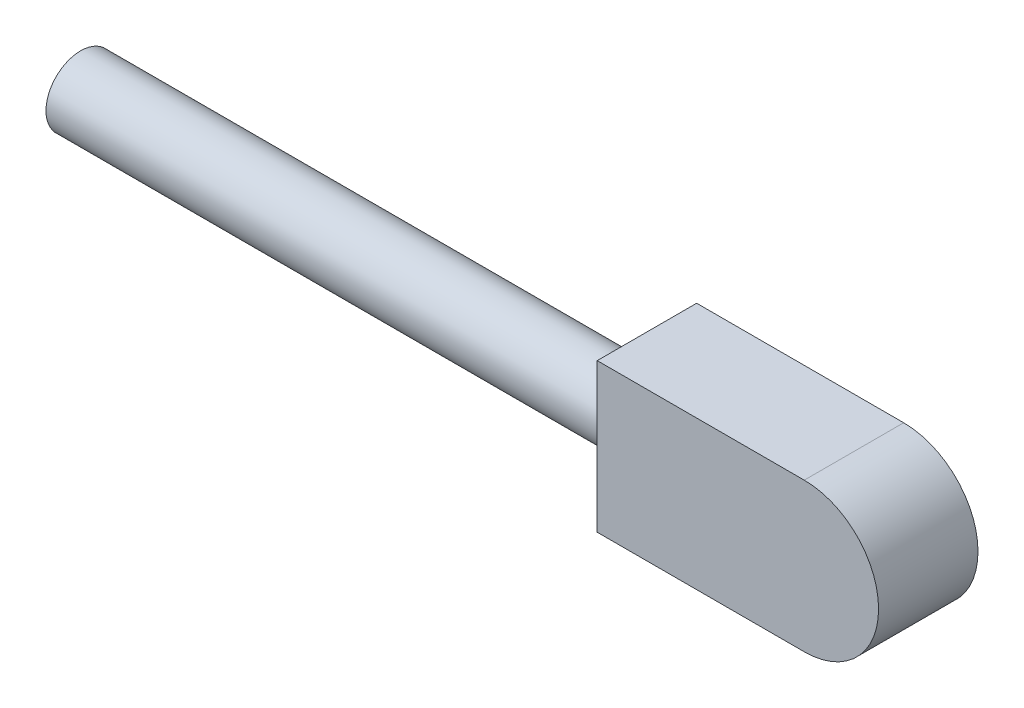
SolidWorks part; units mm, degrees
ref_plane "Front view" through (0, 0, 0) normal (0, 0, 1) x (1, 0, 0)
ref_plane "Top view" through (0, 0, 0) normal (0, 1, 0) x (1, 0, 0)
ref_plane "Side view" through (0, 0, 0) normal (1, 0, 0) x (0, 0, -1)
sketch "Sketch2" plane through (-3856.2967, 0, 6663.1981) normal (0, 1, 0) x (1, 0, 0)
  line L0 (3040.1244, 6663.1981) -> (3856.2967, 6663.1981)
  line L1 (4043.809, 6703.1981) -> (3856.2967, 6703.1981)
  line L2 (4043.809, 6623.1981) -> (3856.2967, 6623.1981)
  line L3 (3856.2967, 6703.1981) -> (3856.2967, 6623.1981)
  line L4 (3856.2967, 6635.6981) -> (3840.2967, 6635.6981)
  line L5 (3851.2967, 6635.6981) -> (3856.2966, 6630.6981)
  line L6 (3856.2967, 6635.6981) -> (3851.2967, 6635.6981)
  line L7 (3856.2966, 6630.6981) -> (3856.2967, 6635.6981)
  line L8 (3856.2967, 6690.6981) -> (3840.2967, 6690.6981)
  line L9 (3856.2966, 6695.6981) -> (3851.2967, 6690.6981)
  line L10 (3856.2967, 6690.6981) -> (3856.2966, 6695.6981)
  line L11 (3851.2967, 6690.6981) -> (3856.2967, 6690.6981)
sketch "Sketch3" plane through (-9482.0455, -5288.969, 0) normal (0, 0, 1) x (1, 0, 0)
  line L1947 (9537.2698, 5438.969) -> (9426.8132, 5502.7412)
  line L1958 (10135.0455, 5288.969) -> (9482.0455, 5288.969)
  line L2105 (9482.0455, 5288.969) -> (9482.0455, 5456.969)
  line L2178 (9651.7783, 5243.9695) -> (9653.5105, 5240.9693)
  line L2179 (9648.3136, 5243.969) -> (9651.7777, 5243.969)
  line L2180 (9646.5818, 5240.9694) -> (9648.3139, 5243.9696)
  line L2181 (9648.3137, 5237.969) -> (9646.5816, 5240.969)
  line L2182 (9651.7777, 5237.9688) -> (9648.3136, 5237.9688)
  line L2183 (9653.5101, 5240.9696) -> (9651.7779, 5237.9694)
  line L2184 (9688.1498, 5312.9695) -> (9689.882, 5315.9697)
  line L2185 (9689.8826, 5309.9691) -> (9688.1505, 5312.9692)
  line L2186 (9693.3463, 5309.9692) -> (9689.8819, 5309.9692)
  line L2187 (9695.0787, 5312.9693) -> (9693.3466, 5309.9693)
  line L2188 (9693.3469, 5315.9693) -> (9695.079, 5312.9693)
  line L2189 (9689.8819, 5315.9692) -> (9693.3462, 5315.9692)
  line L2190 (9689.8826, 5267.97) -> (9693.347, 5267.97)
  line L2191 (9688.1507, 5264.9691) -> (9689.8827, 5267.9692)
  line L2192 (9689.8826, 5261.9696) -> (9688.1504, 5264.9698)
  line L2193 (9693.3469, 5261.9693) -> (9689.8828, 5261.9693)
  line L2194 (9695.0791, 5264.969) -> (9693.347, 5261.969)
  line L2195 (9693.3465, 5267.9698) -> (9695.0787, 5264.9696)
  line L2196 (9648.3126, 5333.9686) -> (9646.5805, 5336.9688)
  line L2197 (9651.7774, 5333.969) -> (9648.3133, 5333.969)
  line L2198 (9653.5092, 5336.9687) -> (9651.777, 5333.9685)
  line L2199 (9651.7773, 5339.9691) -> (9653.5093, 5336.9691)
  line L2200 (9648.3133, 5339.9693) -> (9651.7774, 5339.9693)
  line L2201 (9646.5809, 5336.9685) -> (9648.313, 5339.9687)
  line L2202 (9610.2083, 5309.9681) -> (9606.744, 5309.9681)
  line L2203 (9611.9403, 5312.9689) -> (9610.2083, 5309.9689)
  line L2204 (9610.2084, 5315.9685) -> (9611.9406, 5312.9683)
  line L2205 (9606.7441, 5315.9688) -> (9610.2082, 5315.9688)
  line L2206 (9605.0119, 5312.9691) -> (9606.7439, 5315.9691)
  line L2207 (9606.7445, 5309.9683) -> (9605.0123, 5312.9685)
  line L2208 (9611.9412, 5264.9686) -> (9610.209, 5261.9684)
  line L2209 (9610.2084, 5267.9689) -> (9611.9404, 5264.9689)
  line L2210 (9606.7447, 5267.9689) -> (9610.2091, 5267.9689)
  line L2211 (9605.0123, 5264.9688) -> (9606.7443, 5267.9688)
  line L2212 (9606.7441, 5261.9688) -> (9605.012, 5264.9688)
  line L2213 (9610.2091, 5261.9689) -> (9606.7447, 5261.9689)
  line L2214 (9622.3248, 5378.969) -> (9604.2774, 5378.969)
  line L2215 (9663.9388, 5372.6413) -> (9615.1618, 5337.7863)
  line L2216 (9630.8112, 5348.969) -> (9581.3203, 5348.969)
  line L2217 (9625.0455, 5348.969) -> (9625.0455, 5378.969)
  line L2218 (9630.8112, 5228.969) -> (9581.3203, 5228.969)
  line L2247 (9625.0455, 5171.969) -> (9625.0455, 5228.969)
  line L2256 (9458.0455, 5477.969) -> (9458.0455, 5476.969)
  line L2257 (9432.0455, 5499.0914) -> (9432.0455, 5466.735)
  line L2258 (9477.0455, 5461.969) -> (9473.0455, 5461.969)
  circle A476 centre (9650.0455, 5240.969) radius 6.5
  circle A477 centre (9650.0455, 5336.969) radius 6.5
  arc A478 (9650.1219, 5441.388) -> (9644.6228, 5437.7222) centre (9675.0455, 5398.0427) ccw
  arc A479 (9582.2386, 5353.1583) -> (9605.141, 5378.969) centre (9575.3324, 5382.3526) ccw
  arc A480 (9604.2774, 5378.969) -> (9584.9612, 5364.1542) centre (9604.2774, 5358.969) ccw
  arc A481 (9690.7288, 5426.9076) -> (9622.3248, 5438.969) centre (9622.3248, 5238.969) ccw
  arc A482 (9670.2076, 5370.526) -> (9622.3248, 5378.969) centre (9622.3248, 5238.969) ccw
  circle A483 centre (9650.0455, 5288.969) radius 58
  arc A484 (9615.1741, 5337.7951) -> (9615.1741, 5240.143) centre (9650.0455, 5288.969) ccw
  arc A492 (9584.9612, 5364.1542) -> (9595.6691, 5181.5616) centre (9865.0455, 5288.969) ccw
  arc A498 (9447.0459, 5487.969) -> (9452.0459, 5482.969) centre (9452.0459, 5487.969) ccw
  arc A499 (9458.0455, 5477.969) -> (9453.0455, 5482.969) centre (9453.0455, 5477.969) ccw
  arc A500 (9482.0455, 5456.969) -> (9477.0455, 5461.969) centre (9477.0455, 5456.969) ccw
  arc A501 (9458.0455, 5476.969) -> (9473.0455, 5461.969) centre (9473.0455, 5476.969) ccw
  ellipse E89 centre (9608.4763, 5264.969) end of major axis (9603.8801, 5269.5652) minor radius 6.5
  ellipse E90 centre (9608.4763, 5312.969) end of major axis (9603.8801, 5317.5652) minor radius 6.5
  ellipse E91 centre (9691.6147, 5264.969) end of major axis (9687.0185, 5269.5652) minor radius 6.5
  ellipse E92 centre (9691.6147, 5312.969) end of major axis (9687.0185, 5317.5652) minor radius 6.5
sketch "Sketch4" plane through (0, 0, 0) normal (0, 0, 1) x (1, 0, 0)
  line L0 (0.868, 60) -> (168, 60)
  line L1 (148.7657, 60) -> (99.2748, 60) construction
  line L2 (0.868, -60) -> (168, -60)
  line L4 (0.868, 60) -> (0.868, -60)
  arc A0 (168, -60) -> (168, 60) centre (168, 0) ccw
  circle A1 centre (168, 0) radius 58 construction
  dimension "D1" = 167.132
extrude "Base-Extrude" add sketch "Sketch4" along normal blind 40.132 and the other way blind 40.132
sketch "Sketch5" plane through (0.868, 0, 0) normal (-1, 0, 0) x (0, 0, 1)
  circle A0 centre (0, 0) radius 27.94
  dimension "D1" = 55.88
extrude "Boss-Extrude1" add sketch "Sketch5" along normal blind 457.2
